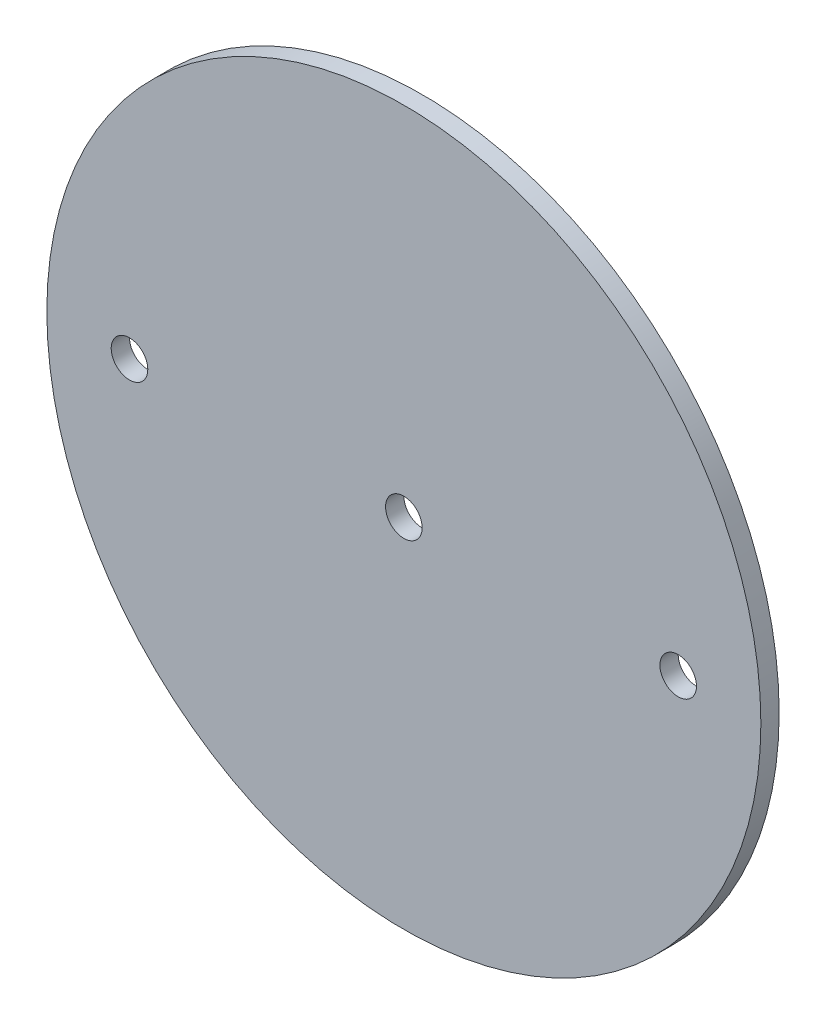
SolidWorks part; units mm, degrees
ref_plane "Front Plane" through (0, 0, 0) normal (0, 0, 1) x (1, 0, 0)
ref_plane "Top Plane" through (0, 0, 0) normal (0, 1, 0) x (1, 0, 0)
ref_plane "Right Plane" through (0, 0, 0) normal (1, 0, 0) x (0, 0, -1)
sketch "Sketch1" plane through (0, 0, 0) normal (0, 0, 1) x (1, 0, 0)
  circle A0 centre (0, 0) radius 61.976
  dimension "D1" = 123.952
extrude "Boss-Extrude1" add sketch "Sketch1" along normal mid plane 3.175
sketch "Sketch2" plane through (0, 0, 1.5875) normal (0, 0, 1) x (1, 0, 0)
  line L0 (-1000, 0) -> (49000, 0) construction
  point P1 (0, 0)
  point P4 (47.625, 0)
  point P5 (-47.625, 0)
  dimension "D1" = 47.625
  dimension "D2" = 95.25
hole_wizard "1/4 (0.25) Diameter Hole1" positions "Sketch2" profile "Sketch3" hole size "1/4" standard "ANSI Inch" end condition through all
sketch "Sketch3" plane through (-47.625, 0, 1.5875) normal (1, 0, 0) x (0, -1, 0)
  line L0 (0, 0) -> (0, 3.175)
  line L1 (0, 3.175) -> (3.175, 3.175)
  line L2 (3.175, 3.175) -> (3.175, 0)
  line L5 (3.175, 0) -> (0, 0)
  line L11 (0, -6.35) -> (0, 107.95) construction
  dimension "Thru Hole Dia." = 6.35
  dimension "Thru Hole Depth" = 3.175
equation "\"AIRFRAME_OD\"= 5.15in"
equation "\"AIRFRAME_ID\"= 5.00in"
equation "\"FLAT_T\"= 0.125in"
equation "\"NOSE_EXP_L\"= 27in"
equation "\"NOSE_SHOULDER_L\"= 5in"
equation "\"MAIN_L\"= 30in"
equation "\"RECO_COUP_L\"= 10in"
equation "\"RECO_SWITCH_L\"= 2in"
equation "\"DROGUE_L\"= 20in"
equation "\"ATS_FORE_COUP_L\"= 5.5in"
equation "\"ATS_AFT_COUP_L\"= 4.5in"
equation "\"LOWER_L\"= 30in"
equation "\"FIN_N\"= 4"
equation "\"CR_AFT_X\"= 0.5in"
equation "\"CR_FORE_X\"= 9.25in"
equation "\"FIN_ROOT\"= 8in"
equation "\"FIN_X\"= 0.75in"
equation "\"MOTOR_OD\"= 3.091in"
equation "\"MOTOR_ID\"= 3.00in"
equation "\"COUPLER_OD\"= 4.998in"
equation "\"COUPLER_ID\"= 4.88in"
equation "\"D1@Sketch1\"=\"COUPLER_ID\""
equation "\"D1@Boss-Extrude1\"=\"FLAT_T\""
equation "\"RECO_ROD_X\"= 3.5in"
equation "\"ATS_ROD_X\"= 3.75in"
equation "\"D1@Sketch2\"=\"ATS_ROD_X\"*0.5"
equation "\"D2@Sketch2\"=\"ATS_ROD_X\""
equation "\"MOTOR_L\"= 14in"
equation "\"MOTOR_LOWER_X\"= 2in"
